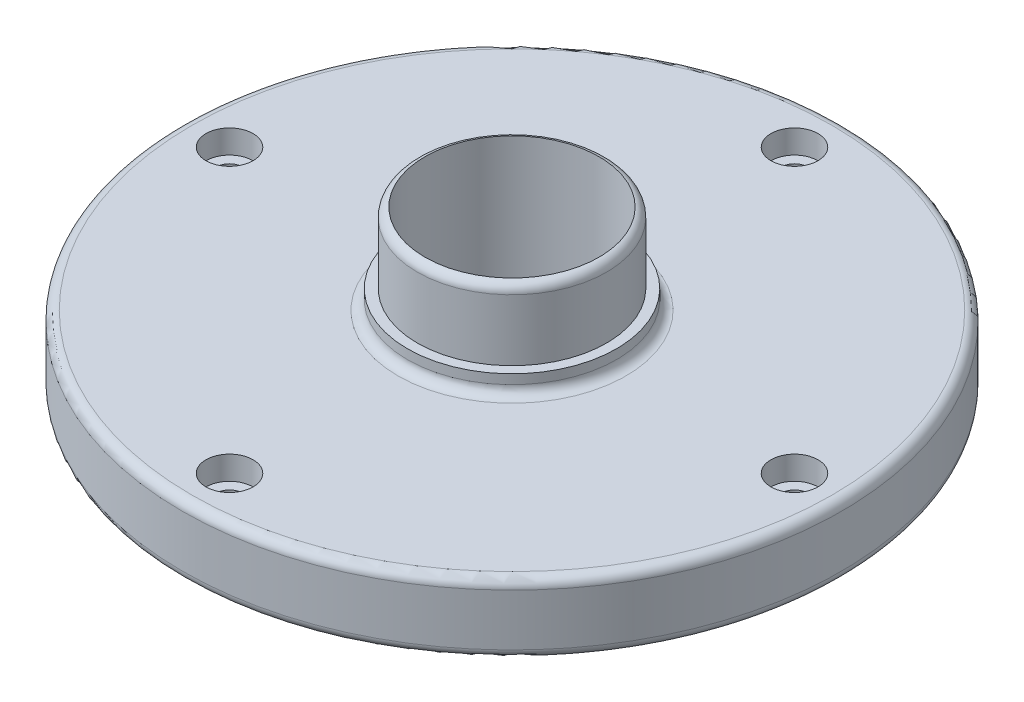
SolidWorks part; units mm, degrees
ref_plane "Front Plane" through (0, 0, 0) normal (0, 0, 1) x (1, 0, 0)
ref_plane "Top Plane" through (0, 0, 0) normal (0, 1, 0) x (1, 0, 0)
ref_plane "Right Plane" through (0, 0, 0) normal (1, 0, 0) x (0, 0, -1)
sketch "Sketch2" plane through (0, 0, 0) normal (0, 1, 0) x (1, 0, 0)
  circle A0 centre (0, 0) radius 70
  dimension "D1" = 140
extrude "Boss-Extrude1" add sketch "Sketch2" along normal blind 15
hole_wizard "CBORE for M5 SHCS1" positions "Sketch21" profile "Sketch22" counterbore size "M5" standard "ANSI Metric" end condition up to next
sketch "Sketch21" plane through (0, 15, 0) normal (0, 1, 0) x (1, 0, 0)
  line L1 (-60, 0) -> (60, 0) construction
  line L3 (0, 60) -> (0, -60) construction
  point P0 (0, 60)
  point P2 (60, 0)
  point P4 (-60, 0)
  point P6 (0, -60)
  point P19 (0, 0)
  point P21 (0, 0)
  dimension "D1" = 120
  dimension "D2" = 120
sketch "Sketch22" plane through (0, 15, -60) normal (1, 0, 0) x (0, 0, 1)
  line L0 (0, 0) -> (0, 15)
  line L1 (0, 15) -> (2.75, 15)
  line L3 (2.75, 15) -> (2.75, 5)
  line L4 (2.75, 5) -> (5, 5)
  line L5 (5, 5) -> (5, 0)
  line L7 (5, 0) -> (0, 0)
  line L11 (0, -6.35) -> (0, 107.95) construction
  dimension "Thru Hole Dia." = 5.5
  dimension "Thru Hole Depth" = 15
  dimension "C'Bore Dia." = 10
  dimension "C'Bore Depth" = 5
sketch "Sketch23" plane through (0, 15, 0) normal (0, 1, 0) x (1, 0, 0)
  circle A0 centre (0, 0) radius 18.5
  circle A1 centre (0, 0) radius 20.1
  dimension "D1" = 37
  dimension "D2" = 40.2
extrude "Boss-Extrude2" add sketch "Sketch23" along normal blind 19
sketch "Sketch24" plane through (0, 15, 0) normal (0, 1, 0) x (1, 0, 0)
  circle A0 centre (0, 0) radius 18.5
  circle A1 centre (0, 0) radius 18.5 construction
extrude "Cut-Extrude4" cut sketch "Sketch24" against normal through all
sketch "Sketch25" plane through (0, 15, 0) normal (0, 1, 0) x (1, 0, 0)
  circle A0 centre (0, 0) radius 22.2
  circle A1 centre (0, 0) radius 20.1
  circle A2 centre (0, 0) radius 20.1 construction
  dimension "D1" = 44.4
extrude "Boss-Extrude3" add sketch "Sketch25" along normal blind 4
fillet "Fillet2" radius 2 4 edges at (0, 34, 20.1) (0, 15, 22.2) (0, 15, 70) (0, 0, 70)
